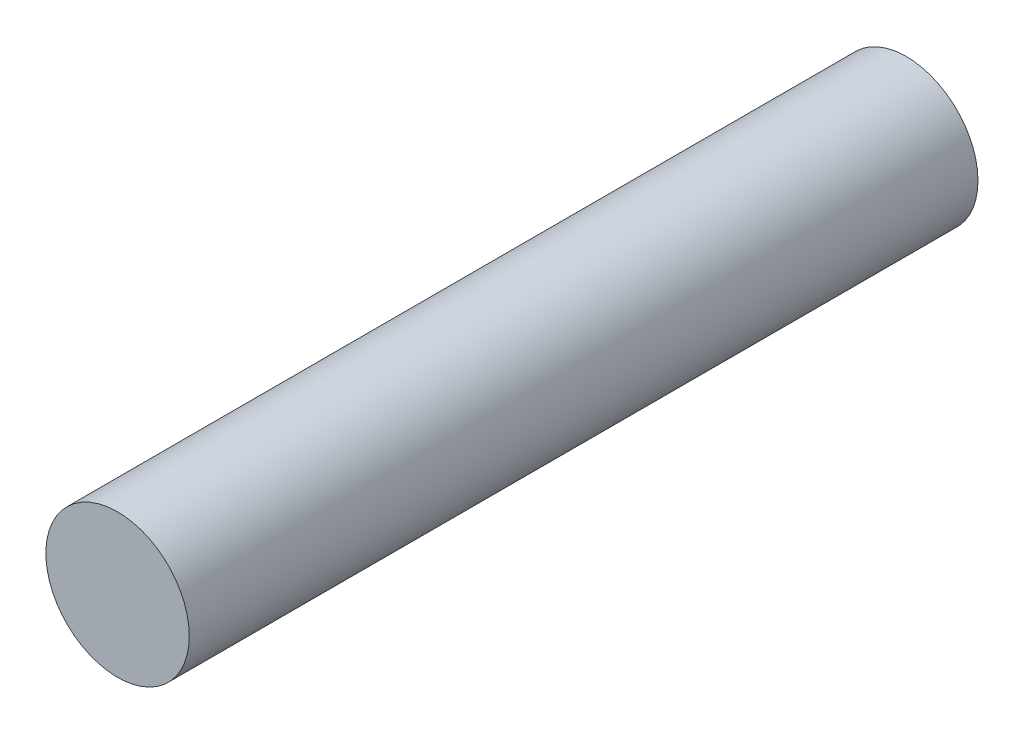
SolidWorks part; units mm, degrees
ref_plane "Plan de face" through (0, 0, 0) normal (0, 0, 1) x (1, 0, 0)
ref_plane "Plan de dessus" through (0, 0, 0) normal (0, 1, 0) x (1, 0, 0)
ref_plane "Plan de droite" through (0, 0, 0) normal (1, 0, 0) x (0, 0, -1)
sketch "Esquisse1" plane through (0, 0, 0) normal (0, 0, 1) x (1, 0, 0)
  circle A0 centre (0, 0) radius 10
  dimension "D1" = 20
extrude "Boss.-Extru.1" add sketch "Esquisse1" along normal blind 55 and the other way blind 55
